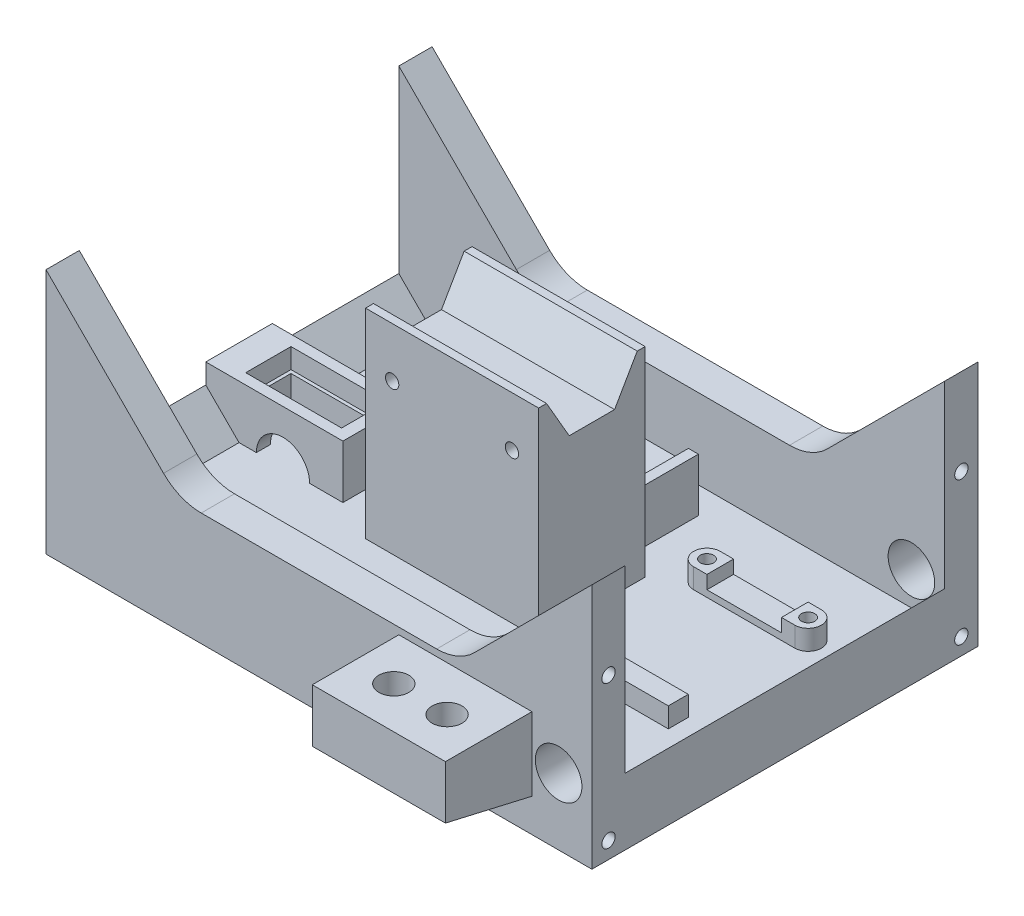
SolidWorks part; units mm, degrees
ref_plane "Plano frontal" through (0, 0, 0) normal (0, 0, 1) x (1, 0, 0)
ref_plane "Plano superior" through (0, 0, 0) normal (0, 1, 0) x (1, 0, 0)
ref_plane "Plano direito" through (0, 0, 0) normal (1, 0, 0) x (0, 0, -1)
sketch "Esboço1" plane through (0, 0, 0) normal (0, 0, 1) x (1, 0, 0)
  line L0 (0, 0) -> (-41, 0)
  line L1 (-41, 0) -> (-41, 60)
  line L2 (-41, 60) -> (-46, 60)
  line L3 (-46, 60) -> (-46, -5)
  line L4 (-46, -5) -> (46, -5)
  line L5 (46, -5) -> (46, 60)
  line L6 (46, 60) -> (41, 60)
  line L7 (41, 60) -> (41, 0)
  line L8 (41, 0) -> (0, 0)
  dimension "D1" = 41
  dimension "D2" = 41
  dimension "D3" = 60
  dimension "D4" = 5
  dimension "D5" = 5
  dimension "D6" = 5
  dimension "D7" = 60
extrude "Ressalto-extrusão1" add sketch "Esboço1" along normal mid plane 58
sketch "Esboço2" plane through (-46, 0, 0) normal (-1, 0, 0) x (0, 0, 1)
  line L0 (29, -5) -> (-29, -5) construction
  circle A0 centre (0, 30) radius 6.5
  dimension "D1" = 13
  dimension "D2" = 35
extrude "Corte-extrusão1" cut sketch "Esboço2" against normal up to next
sketch "Esboço3" plane through (-46, 0, 0) normal (-1, 0, 0) x (0, 0, 1)
  circle A0 centre (0, 30) radius 18
  dimension "D1" = 36
extrude "Corte-extrusão2" cut sketch "Esboço3" against normal blind 2.5
sketch "Esboço5" plane through (-46, 0, 0) normal (-1, 0, 0) x (0, 0, 1)
  line L0 (0, 60) -> (0, -5) construction
  line L1 (29, 60) -> (-29, 60) construction
  line L2 (29, -5) -> (-29, -5) construction
  line L3 (-18, 30) -> (18, 30) construction
  line L4 (-8, 31.5) -> (8, 31.5)
  line L5 (-8, 28.5) -> (8, 28.5)
  arc A0 (-8, 31.5) -> (-8, 28.5) centre (-8, 30) ccw
  arc A1 (8, 31.5) -> (8, 28.5) centre (8, 30) cw
  circle A2 centre (-15.5, 45.5) radius 2
  circle A3 centre (0, 30) radius 18 construction
  circle A7 centre (0, 42) radius 1.5
  circle A8 centre (0, 30) radius 6.5 construction
  circle A9 centre (0, 30) radius 18 construction
  circle A10 centre (0, 18) radius 1.5
  circle A11 centre (0, 54) radius 2
  circle A14 centre (15.5, 45.5) radius 2
  circle A15 centre (15.5, 14.5) radius 2
  circle A16 centre (-15.5, 14.5) radius 2
  circle A17 centre (20.7846, 18) radius 2
  circle A18 centre (-20.7846, 18) radius 2
  point P23 (-2.3598, 32.3598)
  point P43 (1.3625, 32.3598)
  point P44 (0, 30)
  point P45 (0, 30)
  dimension "D1" = 8
  dimension "D2" = 3
  dimension "D3" = 4
  dimension "D4" = 15.5
  dimension "D5" = 15.5
  dimension "D7" = 12
  dimension "D8" = 3
  dimension "D9" = 4
  dimension "D10" = 24
  dimension "D12" = 0
  dimension "D6" = 4
  dimension "D11" = 3
extrude "Corte-extrusão3" cut sketch "Esboço5" against normal up to next (5 mm away)
sketch "Esboço7" plane through (41, 0, 0) normal (-1, 0, 0) x (0, 0, 1)
  circle A0 centre (0, 30) radius 12
  circle A1 centre (-15.5, 45.5) radius 2
  circle A6 centre (15.5, 45.5) radius 2
  circle A7 centre (15.5, 14.5) radius 2
  circle A8 centre (-15.5, 14.5) radius 2
  point P14 (-2.3598, 32.3598)
  point P15 (0, 30)
  dimension "D1" = 24
  dimension "D2" = 15.5
  dimension "D3" = 15.5
  dimension "D4" = 4
  dimension "D5" = 4
extrude "Corte-extrusão4" cut sketch "Esboço7" against normal through all
sketch "Esboço11" plane through (0, 0, 0) normal (0, 1, 0) x (1, 0, 0)
  line L0 (-41, -29) -> (-41, 29) construction
  line L1 (-38.4, 5) -> (-20.4, 5)
  line L2 (-38.4, 5) -> (-38.4, -5)
  line L3 (-38.4, -5) -> (-20.4, -5)
  line L4 (-20.4, 5) -> (-20.4, -5)
  dimension "D1" = 5
  dimension "D2" = 5
  dimension "D3" = 18
  dimension "D4" = 2.6
extrude "Ressalto-extrusão3" add sketch "Esboço11" along normal blind 8
sketch "Esboço12" plane through (0, 8, 0) normal (0, 1, 0) x (1, 0, 0)
  line L0 (-38.4, 5) -> (-38.4, -5) construction
  line L1 (-36.6, -3.4) -> (-22.2, -3.4)
  line L2 (-36.6, -3.4) -> (-36.6, 3.4)
  line L3 (-36.6, 3.4) -> (-22.2, 3.4)
  line L4 (-22.2, -3.4) -> (-22.2, 3.4)
  line L5 (-36.6, -3.4) -> (-22.2, 3.4) construction
  line L6 (-36.6, 3.4) -> (-22.2, -3.4) construction
  line L12 (-20.4, 5) -> (-38.4, 5) construction
  point P0 (-29.4, 0)
  point P7 (-38.4, 0)
  point P11 (-29.4, 5)
  dimension "D1" = 0
  dimension "D2" = 14.4
  dimension "D3" = 6.8
  dimension "D4" = 0
extrude "Corte-extrusão6" cut sketch "Esboço12" against normal blind 3
sketch "Esboço13" plane through (0, 5, 0) normal (0, 1, 0) x (1, 0, 0)
  line L0 (-22.2, 3.4) -> (-36.6, 3.4) construction
  line L1 (-36.1, -2.9) -> (-22.7, -2.9)
  line L2 (-36.1, -2.9) -> (-36.1, 2.9)
  line L3 (-36.1, 2.9) -> (-22.7, 2.9)
  line L4 (-22.7, -2.9) -> (-22.7, 2.9)
  line L5 (-36.1, -2.9) -> (-22.7, 2.9) construction
  line L6 (-36.1, 2.9) -> (-22.7, -2.9) construction
  line L7 (-22.2, -3.4) -> (-22.2, 3.4) construction
  line L8 (-36.6, -3.4) -> (-22.2, -3.4) construction
  point P0 (-29.4, 0)
  point P7 (-29.4, 3.4)
  dimension "D1" = 0
  dimension "D2" = 0.5
  dimension "D3" = 0.5
  dimension "D4" = 0.5
extrude "Corte-extrusão7" cut sketch "Esboço13" against normal up to surface (5 mm away) up to face at (0, 0, 0)
sketch "Esboço14" plane through (0, 0, 5) normal (0, 0, 1) x (1, 0, 0)
  line L0 (-38.4, 0) -> (-20.4, 0) construction
  line L1 (-33.4, 0) -> (-25.4, 0)
  arc A0 (-25.4, 0) -> (-33.4, 0) centre (-29.4, 0) ccw
  dimension "D1" = 8
extrude "Corte-extrusão8" cut sketch "Esboço14" against normal up to next
sketch "Esboço16" plane through (0, 0, 29) normal (0, 0, 1) x (1, 0, 0)
  line L0 (-41, 32) -> (-21, 12)
  line L1 (-41, 0) -> (-41, 60) construction
  line L2 (-21, 12) -> (21, 12)
  line L3 (21, 12) -> (41, 32)
  line L4 (41, 60) -> (41, 0) construction
  line L5 (41, 32) -> (41, 0)
  line L6 (41, 0) -> (-41, 0)
  line L7 (-41, 0) -> (-41, 32)
  dimension "D1" = 32
  dimension "D2" = 32
  dimension "D3" = 12
  dimension "D4" = 20
  dimension "D5" = 20
extrude "Ressalto-extrusão4" add sketch "Esboço16" against normal blind 5
mirror "Espelhar1" about plane through (0, 0, 0) normal (0, 0, 1) of "Ressalto-extrusão4"
sketch "Esboço17" plane through (0, 8, 0) normal (0, 1, 0) x (1, 0, 0)
  line L0 (-41, -24) -> (-41, 24) construction
  line L1 (-38.4, 5) -> (-41, 5)
  line L2 (-38.4, 5) -> (-38.4, -5)
  line L3 (-38.4, -5) -> (-41, -5)
  line L4 (-41, 5) -> (-41, -5)
extrude "Ressalto-extrusão5" add sketch "Esboço17" against normal up to surface (8 mm away) up to face at (0, 0, 0)
chamfer "Chanfro1" distance 5 angle 45 3 edges at (41, 0, 0) (-41, 0, -14.5) (-41, 0, 14.5)
fillet "Filete1" radius 8 8 edges at (21, 12, 26.5) (21, 12, -26.5) (-21, 12, 26.5) (-21, 12, -26.5) (43.5, 60, -29) (43.5, 60, 29) (-43.5, 60, 29) (-43.5, 60, -29)
sketch "Esboço18" plane through (0, 0, 29) normal (0, 0, 1) x (1, 0, 0)
  line L0 (46, -5) -> (46, 52) construction
  line L1 (12, 3) -> (32, 3)
  line L2 (12, 3) -> (12, 11)
  line L3 (12, 11) -> (32, 11)
  line L4 (32, 3) -> (32, 11)
  line L5 (-46, -5) -> (46, -5) construction
  dimension "D1" = 8
  dimension "D2" = 20
  dimension "D3" = 14
  dimension "D4" = 8
extrude "Ressalto-extrusão6" add sketch "Esboço18" along normal blind 13
sketch "Esboço19" plane through (0, 11, 0) normal (0, 1, 0) x (1, 0, 0)
  line L0 (32, -42) -> (12, -42) construction
  circle A0 centre (18, -35.75) radius 2.25
  circle A1 centre (26, -35.75) radius 2.25
  point P6 (22, -42)
  dimension "D1" = 4.5
  dimension "D2" = 4.5
  dimension "D3" = 8
  dimension "D4" = 4
  dimension "D5" = 6.25
extrude "Corte-extrusão9" cut sketch "Esboço19" against normal through all
chamfer "Chanfro2" distance 3 distance2 13 1 edges at (22, 3, 29) first distance on face at (0, 26.1301, 29)
sketch "Esboço20" plane through (0, 11, 0) normal (0, 1, 0) x (1, 0, 0)
  line L0 (18, -31.5) -> (26, -31.5)
  line L1 (18, -40) -> (26, -40)
  arc A0 (18, -31.5) -> (18, -40) centre (18, -35.75) ccw
  arc A1 (26, -40) -> (26, -31.5) centre (26, -35.75) ccw
  dimension "D1" = 8.5
  dimension "D2" = 8.5
extrude "Corte-extrusão10" cut sketch "Esboço20" against normal through all from offset 6 offset against normal yes
sketch "Esboço21" plane through (0, 0, 0) normal (0, 1, 0) x (1, 0, 0)
  line L1 (-14, 8) -> (12, 8)
  line L2 (-14, 8) -> (-14, -8)
  line L3 (-14, -8) -> (12, -8)
  line L4 (12, 8) -> (12, -8)
  dimension "D1" = 8
  dimension "D2" = 8
  dimension "D3" = 14
  dimension "D4" = 12
extrude "Ressalto-extrusão7" add sketch "Esboço21" along normal blind 30
sketch "Esboço22" plane through (12, 0, 0) normal (1, 0, 0) x (0, 0, -1)
  line L1 (6.8127, 30) -> (3.4064, 35.9)
  line L2 (3.4064, 35.9) -> (-3.4064, 35.9)
  line L3 (-3.4064, 35.9) -> (-6.8127, 30)
  line L4 (-6.8127, 30) -> (-3.4064, 24.1)
  line L5 (-3.4064, 24.1) -> (3.4064, 24.1)
  line L6 (3.4064, 24.1) -> (6.8127, 30)
  circle A0 centre (0, 30) radius 5.9 construction
  dimension "D1" = 11.8
  dimension "D2" = 30
extrude "Corte-extrusão11" cut sketch "Esboço22" against normal up to surface (26 mm away) up to face at (-14, 15, 0)
sketch "Esboço24" plane through (0, 0, 0) normal (0, 1, 0) x (1, 0, 0)
  line L0 (17.2823, 14) -> (32.4823, 14)
  line L1 (17.2823, 10) -> (32.4823, 10)
  line L2 (-36, 24) -> (36, 24) construction
  line L4 (16.2823, -7) -> (33.4823, -7)
  line L5 (16.2823, -7) -> (16.2823, -10)
  line L6 (16.2823, -10) -> (33.4823, -10)
  line L7 (33.4823, -7) -> (33.4823, -10)
  circle A0 centre (17.2823, 12) radius 1
  circle A1 centre (32.4823, 12) radius 1
  arc A2 (17.2823, 14) -> (17.2823, 10) centre (17.2823, 12) ccw
  arc A3 (32.4823, 10) -> (32.4823, 14) centre (32.4823, 12) ccw
  dimension "D1" = 15.2
  dimension "D2" = 2
  dimension "D3" = 2
  dimension "D4" = 4
  dimension "D5" = 4
  dimension "D6" = 10
  dimension "D7" = 3
  dimension "D8" = 17
  dimension "D9" = 1
  dimension "D10" = 1
extrude "Ressalto-extrusão8" add sketch "Esboço24" along normal blind 3
sketch "Esboço25" plane through (0, 3, 0) normal (0, 1, 0) x (1, 0, 0)
  line L0 (32.4823, 14) -> (17.2823, 14) construction
  line L1 (19.2823, 14) -> (30.4823, 14)
  line L2 (19.2823, 14) -> (19.2823, 10)
  line L3 (19.2823, 10) -> (30.4823, 10)
  line L4 (30.4823, 14) -> (30.4823, 10)
  line L5 (17.2823, 10) -> (32.4823, 10) construction
  circle A0 centre (17.2823, 12) radius 1 construction
  circle A1 centre (32.4823, 12) radius 1 construction
  dimension "D1" = 2
  dimension "D2" = 2
extrude "Corte-extrusão12" cut sketch "Esboço25" against normal blind 2
sketch "Esboço26" plane through (0, 0, 29) normal (0, 0, 1) x (1, 0, 0)
  line L0 (-46, -5) -> (46, -5) construction
  line L1 (46, -5) -> (46, 52) construction
  circle A0 centre (36, 5) radius 3.5
  dimension "D1" = 7
  dimension "D2" = 10
  dimension "D3" = 10
extrude "Corte-extrusão13" cut sketch "Esboço26" against normal up to surface (5 mm away) up to face at (0, 12.5561, 24)
sketch "Esboço27" plane through (0, 0, 0) normal (0, 1, 0) x (1, 0, 0)
  line L0 (-41, -21) -> (-41, 21) construction
  line L1 (-16, 20) -> (8, 20)
  line L2 (-16, 20) -> (-16, 12)
  line L3 (-16, 12) -> (8, 12)
  line L4 (8, 20) -> (8, 12)
  line L5 (17.6863, 24) -> (-17.6863, 24) construction
  dimension "D1" = 8
  dimension "D2" = 24
  dimension "D3" = 25
  dimension "D4" = 4
extrude "Ressalto-extrusão9" add sketch "Esboço27" along normal blind 6
sketch "Esboço28" plane through (0, 6, 0) normal (0, 1, 0) x (1, 0, 0)
  line L0 (-16, 12) -> (8, 12) construction
  line L1 (-16, 20) -> (-14.5, 20)
  line L2 (-16, 20) -> (-16, 12)
  line L3 (-16, 12) -> (-14.5, 12)
  line L4 (-14.5, 20) -> (-14.5, 12)
  line L6 (8, 20) -> (6.5, 20)
  line L7 (8, 20) -> (8, 12)
  line L8 (8, 12) -> (6.5, 12)
  line L9 (6.5, 20) -> (6.5, 12)
  dimension "D1" = 1.5
  dimension "D2" = 1.5
extrude "Ressalto-extrusão10" add sketch "Esboço28" along normal blind 2
sketch "Esboço31" plane through (0, 0, 8) normal (0, 0, 1) x (1, 0, 0)
  line L0 (-14, 30) -> (12, 30) construction
  line L1 (-14, 30) -> (-14, 0) construction
  line L2 (12, 30) -> (12, 0) construction
  circle A0 centre (-10, 22.5) radius 1
  circle A1 centre (8, 22.5) radius 1
  dimension "D1" = 2
  dimension "D2" = 2
  dimension "D3" = 7.5
  dimension "D4" = 7.5
  dimension "D5" = 4
  dimension "D6" = 4
extrude "Corte-extrusão14" cut sketch "Esboço31" against normal through all
sketch "Esboço32" plane through (-46, 0, 0) normal (-1, 0, 0) x (0, 0, 1)
  line L0 (0, -5) -> (0, 60) construction
  line L1 (29, -5) -> (-29, -5) construction
  line L2 (21, 60) -> (-21, 60) construction
  line L3 (-29, 52) -> (-29, -5) construction
  circle A0 centre (-26.5, -2.5) radius 1
  circle A1 centre (-26.5, 19) radius 1
  circle A2 centre (26.5, 19) radius 1
  circle A3 centre (26.5, -2.5) radius 1
  dimension "D1" = 2
  dimension "D2" = 2
  dimension "D3" = 2.5
  dimension "D4" = 0
  dimension "D5" = 24
  dimension "D6" = 2.5
extrude "Corte-extrusão15" cut sketch "Esboço32" against normal blind 12
sketch "Esboço33" plane through (-46, 0, 0) normal (-1, 0, 0) x (0, 0, 1)
  line L0 (0, 60) -> (0, -5) construction
  line L1 (21, 60) -> (-21, 60) construction
  line L2 (29, -5) -> (-29, -5) construction
  circle A0 centre (-26.5, -2.5) radius 1.25
  circle A1 centre (-26.5, 19) radius 1.25
  circle A2 centre (26.5, 19) radius 1.25
  circle A3 centre (26.5, -2.5) radius 1.25
  dimension "D1" = 2.5
  dimension "D2" = 2.5
extrude "Corte-extrusão16" cut sketch "Esboço33" against normal blind 5
sketch "Esboço34" plane through (-46, 0, 0) normal (-1, 0, 0) x (0, 0, 1)
  line L0 (-26.5, -0.25) -> (-29, -0.25)
  line L1 (-24.25, -2.5) -> (-24.25, -5)
  line L2 (-29, -0.25) -> (-29, -5)
  line L4 (-29, -5) -> (-24.25, -5)
  line L6 (-26.5, 21.25) -> (-29, 21.25)
  line L7 (-26.5, 16.75) -> (-29, 16.75)
  line L8 (-29, 52) -> (-29, -5) construction
  line L9 (-29, 16.75) -> (-29, 21.25)
  line L10 (0, -5) -> (0, 60) construction
  line L11 (29, -5) -> (-29, -5) construction
  line L12 (21, 60) -> (-21, 60) construction
  line L13 (29, 16.75) -> (29, 21.25)
  line L14 (26.5, 16.75) -> (29, 16.75)
  line L15 (26.5, 21.25) -> (29, 21.25)
  line L16 (29, -5) -> (24.25, -5)
  line L17 (29, -0.25) -> (29, -5)
  line L18 (24.25, -2.5) -> (24.25, -5)
  line L19 (26.5, -0.25) -> (29, -0.25)
  arc A0 (-26.5, 16.75) -> (-26.5, 21.25) centre (-26.5, 19) ccw
  arc A1 (-24.25, -2.5) -> (-26.5, -0.25) centre (-26.5, -2.5) ccw
  arc A2 (24.25, -2.5) -> (26.5, -0.25) centre (26.5, -2.5) cw
  arc A3 (26.5, 16.75) -> (26.5, 21.25) centre (26.5, 19) cw
  dimension "D1" = 4.5
  dimension "D2" = 4.5
extrude "Corte-extrusão17" cut sketch "Esboço34" against normal blind 2
mirror "Espelhar2" about plane through (0, 0, 0) normal (1, 0, 0) of "Corte-extrusão17", "Corte-extrusão16", "Corte-extrusão15"
sketch "Esboço38" plane through (41, 0, 0) normal (-1, 0, 0) x (0, 0, 1)
  circle A0 centre (0, 30) radius 62.5488
extrude "Corte-extrusão20" cut sketch "Esboço38" against normal through all
sketch "Esboço39" plane through (-41, 0, 0) normal (1, 0, 0) x (0, 0, -1)
  circle A0 centre (0, 30) radius 54.5836
extrude "Corte-extrusão21" cut sketch "Esboço39" against normal through all
mirror "Espelhar3" about plane through (0, 0, 0) normal (0, 0, 1) of "Corte-extrusão13"
